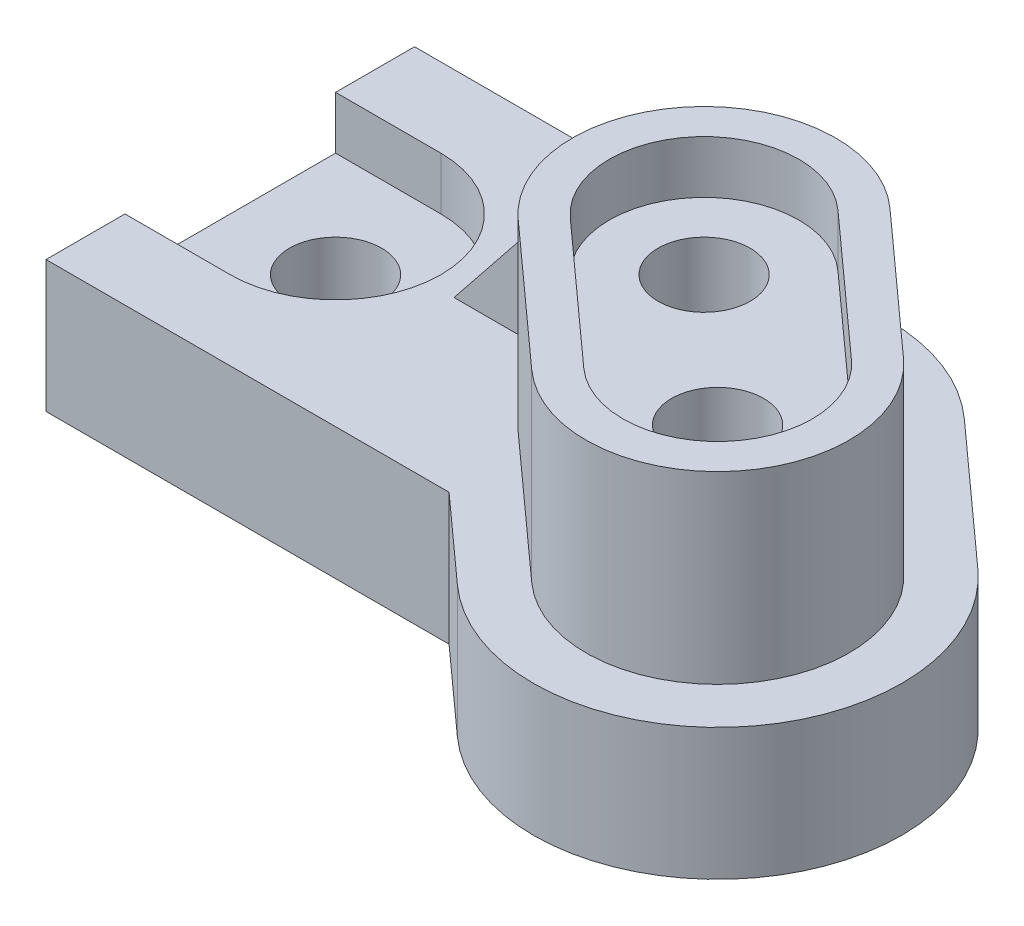
SolidWorks part; units mm, degrees
ref_plane "Front Plane" through (0, 0, 0) normal (0, 0, 1) x (1, 0, 0)
ref_plane "Top Plane" through (0, 0, 0) normal (0, 1, 0) x (1, 0, 0)
ref_plane "Right Plane" through (0, 0, 0) normal (1, 0, 0) x (0, 0, -1)
sketch "Sketch1" plane through (0, 0, 0) normal (0, 1, 0) x (1, 0, 0)
  line L0 (90, 35) -> (116, 11.5693) construction
  line L1 (0, 0) -> (76.5561, 0)
  line L2 (0, 0) -> (0, 70)
  line L3 (0, 70) -> (90, 70)
  line L5 (113.4307, 61) -> (139.4307, 37.5693)
  line L6 (66.5693, 9) -> (92.5693, -14.4307)
  arc A0 (113.4307, 61) -> (66.5693, 9) centre (90, 35) ccw
  arc A1 (92.5693, -14.4307) -> (139.4307, 37.5693) centre (116, 11.5693) ccw
  point P7 (103, 23.2846)
  dimension "D1" = 70
  dimension "D2" = 35
  dimension "D3" = 90
  dimension "D4" = 90
  dimension "D5" = 35
  dimension "D6" = 103
extrude "Boss-Extrude1" add sketch "Sketch1" along normal blind 25 contours A0 L3 L2 L1 L6 | L6 A1 L5 A0 region at (31.5211, 0, -35.1621) region at (103, 0, -23.2846)
sketch "Sketch2" plane through (0, 25, 0) normal (0, 1, 0) x (1, 0, 0)
  line L0 (116, 11.5693) -> (90, 35) construction
  line L1 (99.2638, -7.0022) -> (73.2638, 16.4286)
  line L2 (132.7362, 30.1407) -> (106.7362, 53.5714)
  line L3 (113.4307, 61) -> (139.4307, 37.5693) construction
  arc A0 (99.2638, -7.0022) -> (132.7362, 30.1407) centre (116, 11.5693) ccw
  arc A1 (106.7362, 53.5714) -> (73.2638, 16.4286) centre (90, 35) ccw
  point P4 (103, 23.2846)
  dimension "D1" = 10
extrude "Boss-Extrude2" add sketch "Sketch2" along normal blind 35
sketch "Sketch3" plane through (0, 60, 0) normal (0, 1, 0) x (1, 0, 0)
  line L0 (116, 11.5693) -> (90, 35) construction
  line L1 (103.9499, -1.8022) -> (77.9499, 21.6286)
  line L2 (128.0501, 24.9407) -> (102.0501, 48.3714)
  line L3 (132.7362, 30.1407) -> (106.7362, 53.5714) construction
  arc A0 (103.9499, -1.8022) -> (128.0501, 24.9407) centre (116, 11.5693) ccw
  arc A1 (102.0501, 48.3714) -> (77.9499, 21.6286) centre (90, 35) ccw
  point P4 (103, 23.2846)
  dimension "D1" = 7
extrude "Cut-Extrude1" cut sketch "Sketch3" against normal blind 10
sketch "Sketch4" plane through (0, 50, 0) normal (0, 1, 0) x (1, 0, 0)
  point P0 (90, 35)
  point P1 (116, 11.5693)
hole_wizard "M20 Tapped Hole1" positions "3DSketch1" profile "Sketch5" tap size "M20" standard "ISO"
sketch3d "3DSketch1"
  point P0 (90, 50, -35)
  point P3 (116, 50, -11.5693)
sketch "Sketch5" plane through (90, 50, -35) normal (1, 0, 0) x (0, 0, 1)
  line L0 (0, 0) -> (0, 25.2575)
  line L1 (0, 25.2575) -> (8.75, 20)
  line L2 (8.75, 20) -> (8.75, 0)
  line L5 (8.75, 0) -> (0, 0)
  line L10 (0, 25.2575) -> (-8.75, 20) construction
  line L11 (0, -6.35) -> (0, 107.95) construction
  dimension "Tap Drill Dia." = 17.5
  dimension "Tap Drill Depth" = 20
  dimension "Drill Angle" = 118
cosmetic thread "Hole Thread1" parameters "D1"=20, "D2"=20
cosmetic thread "Hole Thread2" parameters "D1"=20, "D2"=20
sketch "Sketch6" plane through (0, 25, 0) normal (0, 1, 0) x (1, 0, 0)
  point P0 (20, 35)
  dimension "D1" = 20
  dimension "D2" = 35
hole_wizard "M20 Tapped Hole2" positions "3DSketch2" profile "Sketch7" tap size "M20" standard "ISO"
sketch3d "3DSketch2"
  point P0 (20, 25, -35)
sketch "Sketch7" plane through (20, 25, -35) normal (1, 0, 0) x (0, 0, 1)
  line L0 (0, 0) -> (0, 32.7575)
  line L1 (0, 32.7575) -> (8.75, 27.5)
  line L2 (8.75, 27.5) -> (8.75, 0)
  line L5 (8.75, 0) -> (0, 0)
  line L10 (0, 32.7575) -> (-8.75, 27.5) construction
  line L11 (0, -6.35) -> (0, 107.95) construction
  dimension "Tap Drill Dia." = 17.5
  dimension "Tap Drill Depth" = 27.5
  dimension "Drill Angle" = 118
cosmetic thread "Hole Thread3" parameters "D1"=20, "D2"=20
sketch "Sketch8" plane through (0, 25, 0) normal (0, 1, 0) x (1, 0, 0)
  line L0 (0, 55) -> (20, 55)
  line L1 (0, 0) -> (0, 70) construction
  line L2 (0, 15) -> (20, 15)
  line L3 (0, 15) -> (0, 55)
  arc A0 (20, 55) -> (20, 15) centre (20, 35) cw
  circle M1 centre (20, 35) radius 8.75
  line M4 (0, 70) -> (0, 0)
  dimension "D1" = 20
  dimension "D2" = 15
  dimension "D3" = 20
  dimension "D4" = 15
extrude "Cut-Extrude2" cut sketch "Sketch8" against normal blind 10 contours A0 L0 L2 M4 M1 region at (10, 25, -54.4343)
sketch "Sketch9" plane through (0, 25, 0) normal (0, 1, 0) x (1, 0, 0)
  line L0 (65, 35) -> (45, 35)
  line L2 (45, 32.5) -> (65, 32.5)
  line L3 (45, 32.5) -> (45, 37.5)
  line L4 (45, 37.5) -> (65, 37.5)
  line L5 (65, 32.5) -> (65, 37.5)
  line L6 (45, 32.5) -> (65, 37.5) construction
  line L7 (45, 37.5) -> (65, 32.5) construction
  arc A0 (106.7362, 53.5714) -> (73.2638, 16.4286) centre (90, 35) ccw construction
  arc A1 (106.7362, 53.5714) -> (73.2638, 16.4286) centre (90, 35) ccw construction
  point P9 (55, 35)
  dimension "D1" = 20
  dimension "D2" = 20
  dimension "D3" = 5
extrude "Boss-Extrude4" add sketch "Sketch9" along normal blind 25 separate body contours L2 L5 L0 L3 | L0 L5 L4 L3 region at (55, 25, -33.75) region at (55, 25, -36.25)
fillet "Chamfer1" radius 20 1 edges at (45, 50, -35) profile chamfer first distance on face at (55, 50, -35)
